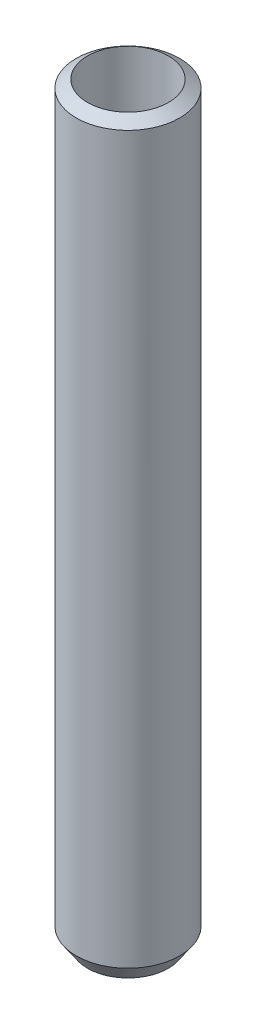
SolidWorks part; units mm, degrees
ref_plane "Front Plane" through (0, 0, 0) normal (0, 0, 1) x (1, 0, 0)
ref_plane "Top Plane" through (0, 0, 0) normal (0, 1, 0) x (1, 0, 0)
ref_plane "Right Plane" through (0, 0, 0) normal (1, 0, 0) x (0, 0, -1)
sketch "Sketch1" plane through (0, 0, 0) normal (0, 1, 0) x (1, 0, 0)
  circle A0 centre (0, 0) radius 25
  dimension "SHAFT_OD" = 50
extrude "Boss-Extrude1" add sketch "Sketch1" along normal blind 364.6927
sketch "Sketch2" plane through (0, 0, 0) normal (0, 1, 0) x (1, 0, 0)
  circle A0 centre (0, 0) radius 19.544
  dimension "BORE_D" = 39.0881
extrude "Cut-Extrude1" cut sketch "Sketch2" along normal through all
chamfer "Chamfer1" distance 5.6107 angle 55.565 2 edges at (0, 364.6927, 25) (0, 0, 25) first distance on face at (0, 364.6927, 25) first distance on face at (0, 0, 19.544)
